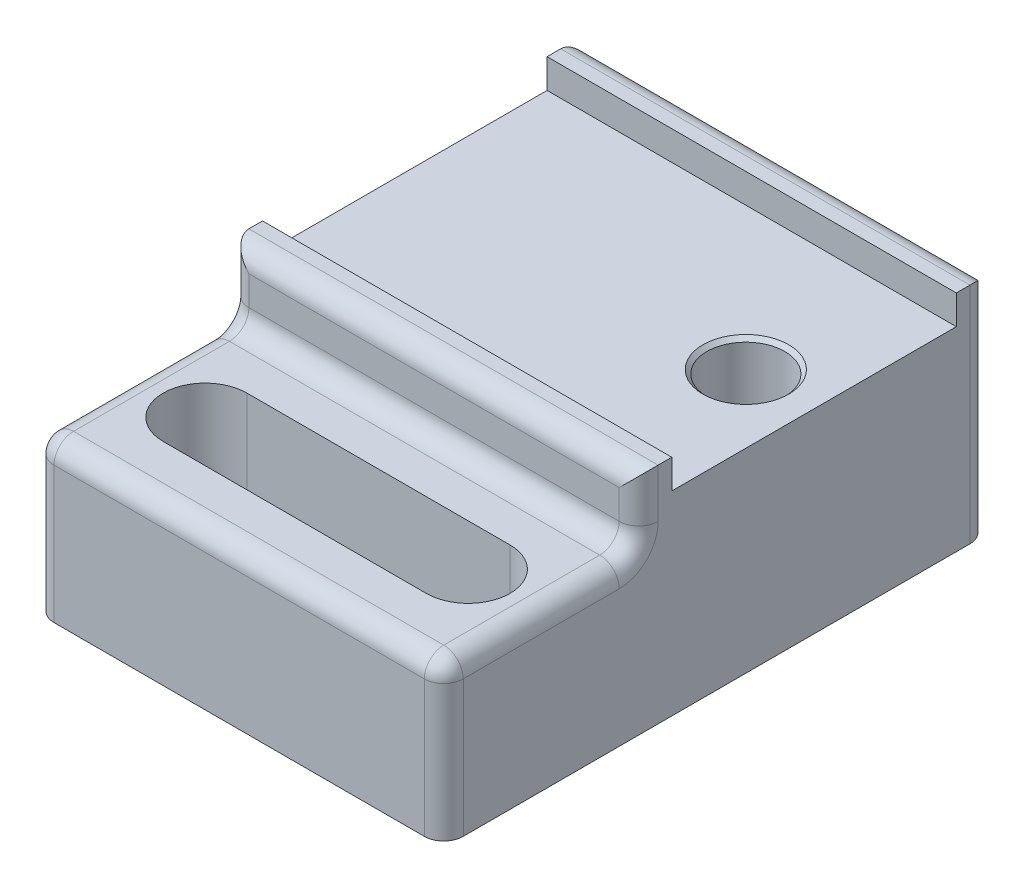
SolidWorks part; units mm, degrees
ref_plane "Front Plane" through (0, 0, 0) normal (0, 0, 1) x (1, 0, 0)
ref_plane "Top Plane" through (0, 0, 0) normal (0, 1, 0) x (1, 0, 0)
ref_plane "Right Plane" through (0, 0, 0) normal (1, 0, 0) x (0, 0, -1)
sketch "Sketch1" plane through (0, 0, 0) normal (0, 1, 0) x (1, 0, 0)
  line L1 (-10.5, 7.3) -> (10.5, 7.3)
  line L2 (-10.5, 7.3) -> (-10.5, -7.3)
  line L3 (-10.5, -7.3) -> (10.5, -7.3)
  line L4 (10.5, 7.3) -> (10.5, -7.3)
  line L5 (-10.5, 7.3) -> (10.5, -7.3) construction
  line L6 (-10.5, -7.3) -> (10.5, 7.3) construction
  line L7 (-10.5, 9) -> (10.5, 9)
  line L8 (-10.5, 9) -> (-10.5, -9)
  line L9 (-10.5, -9) -> (10.5, -9)
  line L10 (10.5, 9) -> (10.5, -9)
  line L11 (-10.5, 9) -> (10.5, -9) construction
  line L12 (-10.5, -9) -> (10.5, 9) construction
  point P0 (0, 0)
  point P6 (0, 0)
  dimension "D1" = 21
  dimension "D2" = 14.6
  dimension "D3" = 18
extrude "Boss-Extrude1" add sketch "Sketch1" along normal blind 10 contours L4 L1 L2 L3 region at (0, 0, 0)
extrude "Boss-Extrude2" add sketch "Sketch1<3>" along normal blind 11.5 contours L10 L3 L8 L9 | L10 L7 L8 L1 region at (0, 0, -8.15) region at (0, 0, 8.15)
sketch "Sketch1<3>" plane through (0, 0, 0) normal (0, 1, 0) x (1, 0, 0) same geometry as "Sketch1"
sketch "Sketch3" plane through (0, 0, 0) normal (0, 1, 0) x (1, 0, 0)
  line L1 (-10.5, -9) -> (10.5, -9)
  line L2 (-10.5, -9) -> (-10.5, -19)
  line L3 (-10.5, -19) -> (10.5, -19)
  line L4 (10.5, -9) -> (10.5, -19)
  dimension "D1" = 10
extrude "Boss-Extrude4" add sketch "Sketch3" along normal blind 8
fillet "Fillet1" radius 1 12 edges at (10.5, 8, 14) (-10.5, 9.75, 9) (10.5, 5.75, -9) (0, 11.5, 9) (-10.5, 5.75, -9) (0, 11.5, -9) (-10.5, 4, 19) (10.5, 4, 19) (0, 8, 19) (10.5, 9.75, 9) (-10.5, 8, 14) (0, 8, 9)
sketch "Sketch4" plane through (0, 8, 0) normal (0, 1, 0) x (1, 0, 0)
  line L0 (-9.5, -14) -> (9.5, -14) construction
  line L1 (-9.5, -10) -> (-9.5, -18) construction
  line L2 (9.5, -18) -> (9.5, -10) construction
  line L3 (-6.75, -14) -> (6.75, -14) construction
  line L4 (-6.75, -11.85) -> (6.75, -11.85)
  line L5 (-6.75, -16.15) -> (6.75, -16.15)
  arc A0 (-6.75, -11.85) -> (-6.75, -16.15) centre (-6.75, -14) ccw
  arc A1 (6.75, -16.15) -> (6.75, -11.85) centre (6.75, -14) ccw
  point P8 (0, -14)
  dimension "D3" = 2.15
  dimension "D1" = 2.75
  dimension "D2" = 2.75
extrude "Cut-Extrude1" cut sketch "Sketch4" against normal through all
sketch "Sketch5" plane through (0, 10, 0) normal (0, 1, 0) x (1, 0, 0)
  line L0 (10.5, 7.3) -> (10.5, -7.3) construction
  circle A0 centre (7, 0) radius 2
  dimension "D1" = 4
  dimension "D2" = 3.5
extrude "Cut-Extrude2" cut sketch "Sketch5" against normal blind 6.8
chamfer "Chamfer1" distance 0.2 angle 45 1 edges at (7, 10, 2)
